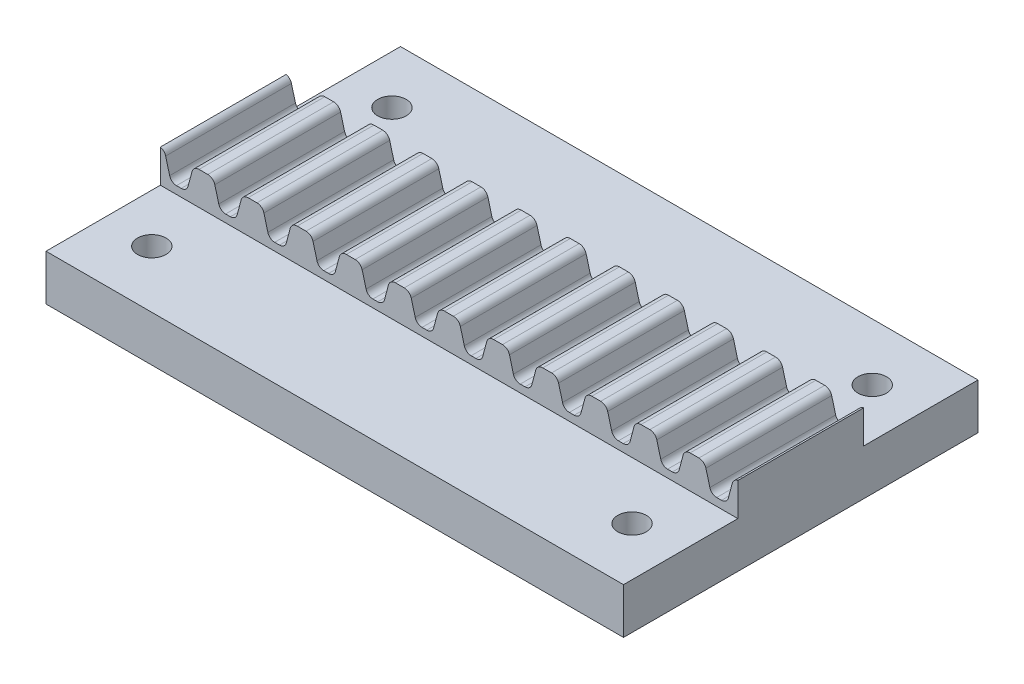
SolidWorks part; units mm, degrees
ref_plane "Front Plane" through (0, 0, 0) normal (0, 0, 1) x (1, 0, 0)
ref_plane "Top Plane" through (0, 0, 0) normal (0, 1, 0) x (1, 0, 0)
ref_plane "Right Plane" through (0, 0, 0) normal (1, 0, 0) x (0, 0, -1)
sketch "Sketch3" plane through (0, 0, 0) normal (1, 0, 0) x (0, 0, -1)
  line L1 (0, 0) -> (22, 0)
  line L2 (0, 0) -> (0, 5.7785)
  line L3 (0, 5.7785) -> (22, 5.7785)
  line L4 (22, 0) -> (22, 5.7785)
extrude "Boss-Extrude2" add sketch "Sketch3" against normal blind 101
sketch "Sketch5" plane through (0, 0, 0) normal (0, 0, -1) x (-1, 0, 0)
  line L0 (1.6741, 2.2584) -> (0.4213, 6.9342)
  line L1 (3.7054, 1.3462) -> (2.863, 1.3462)
  line L5 (4.8943, 2.2584) -> (6.1471, 6.9342)
  line L6 (0.4213, 6.9342) -> (6.1471, 6.9342)
  line L7 (10.2631, 2.2584) -> (9.0103, 6.9342)
  line L8 (9.0103, 6.9342) -> (14.7361, 6.9342)
  line L9 (13.4833, 2.2584) -> (14.7361, 6.9342)
  line L10 (12.2944, 1.3462) -> (11.452, 1.3462)
  line L11 (18.8521, 2.2584) -> (17.5993, 6.9342)
  line L12 (17.5993, 6.9342) -> (23.3251, 6.9342)
  line L13 (22.0723, 2.2584) -> (23.3251, 6.9342)
  line L14 (20.8834, 1.3462) -> (20.041, 1.3462)
  line L15 (27.4411, 2.2584) -> (26.1883, 6.9342)
  line L16 (26.1883, 6.9342) -> (31.9141, 6.9342)
  line L17 (30.6613, 2.2584) -> (31.9141, 6.9342)
  line L18 (29.4724, 1.3462) -> (28.63, 1.3462)
  line L19 (36.0301, 2.2584) -> (34.7773, 6.9342)
  line L20 (34.7773, 6.9342) -> (40.5031, 6.9342)
  line L21 (39.2503, 2.2584) -> (40.5031, 6.9342)
  line L22 (38.0614, 1.3462) -> (37.219, 1.3462)
  line L23 (44.6191, 2.2584) -> (43.3663, 6.9342)
  line L24 (43.3663, 6.9342) -> (49.0921, 6.9342)
  line L25 (47.8393, 2.2584) -> (49.0921, 6.9342)
  line L26 (46.6504, 1.3462) -> (45.808, 1.3462)
  line L27 (53.2081, 2.2584) -> (51.9553, 6.9342)
  line L28 (51.9553, 6.9342) -> (57.6811, 6.9342)
  line L29 (56.4283, 2.2584) -> (57.6811, 6.9342)
  line L30 (55.2394, 1.3462) -> (54.397, 1.3462)
  line L31 (61.7971, 2.2584) -> (60.5443, 6.9342)
  line L32 (60.5443, 6.9342) -> (66.2701, 6.9342)
  line L33 (65.0173, 2.2584) -> (66.2701, 6.9342)
  line L34 (63.8284, 1.3462) -> (62.986, 1.3462)
  line L35 (70.3861, 2.2584) -> (69.1333, 6.9342)
  line L36 (69.1333, 6.9342) -> (74.8591, 6.9342)
  line L37 (73.6063, 2.2584) -> (74.8591, 6.9342)
  line L38 (72.4174, 1.3462) -> (71.575, 1.3462)
  line L39 (78.9751, 2.2584) -> (77.7223, 6.9342)
  line L40 (77.7223, 6.9342) -> (83.4481, 6.9342)
  line L41 (82.1953, 2.2584) -> (83.4481, 6.9342)
  line L42 (81.0064, 1.3462) -> (80.164, 1.3462)
  line L43 (87.5641, 2.2584) -> (86.3113, 6.9342)
  line L44 (86.3113, 6.9342) -> (92.0371, 6.9342)
  line L45 (90.7843, 2.2584) -> (92.0371, 6.9342)
  line L46 (89.5954, 1.3462) -> (88.753, 1.3462)
  line L47 (96.1531, 2.2584) -> (94.9003, 6.9342)
  line L48 (94.9003, 6.9342) -> (100.6261, 6.9342)
  line L49 (99.3733, 2.2584) -> (100.6261, 6.9342)
  line L50 (98.1844, 1.3462) -> (97.342, 1.3462)
  arc A0 (3.7054, 1.3462) -> (4.8943, 2.2584) centre (3.7054, 2.577) ccw
  arc A1 (2.863, 1.3462) -> (1.6741, 2.2584) centre (2.863, 2.577) cw
  arc A2 (12.2944, 1.3462) -> (13.4833, 2.2584) centre (12.2944, 2.577) ccw
  arc A3 (11.452, 1.3462) -> (10.2631, 2.2584) centre (11.452, 2.577) cw
  arc A4 (20.8834, 1.3462) -> (22.0723, 2.2584) centre (20.8834, 2.577) ccw
  arc A5 (20.041, 1.3462) -> (18.8521, 2.2584) centre (20.041, 2.577) cw
  arc A6 (29.4724, 1.3462) -> (30.6613, 2.2584) centre (29.4724, 2.577) ccw
  arc A7 (28.63, 1.3462) -> (27.4411, 2.2584) centre (28.63, 2.577) cw
  arc A8 (38.0614, 1.3462) -> (39.2503, 2.2584) centre (38.0614, 2.577) ccw
  arc A9 (37.219, 1.3462) -> (36.0301, 2.2584) centre (37.219, 2.577) cw
  arc A10 (46.6504, 1.3462) -> (47.8393, 2.2584) centre (46.6504, 2.577) ccw
  arc A11 (45.808, 1.3462) -> (44.6191, 2.2584) centre (45.808, 2.577) cw
  arc A12 (55.2394, 1.3462) -> (56.4283, 2.2584) centre (55.2394, 2.577) ccw
  arc A13 (54.397, 1.3462) -> (53.2081, 2.2584) centre (54.397, 2.577) cw
  arc A14 (63.8284, 1.3462) -> (65.0173, 2.2584) centre (63.8284, 2.577) ccw
  arc A15 (62.986, 1.3462) -> (61.7971, 2.2584) centre (62.986, 2.577) cw
  arc A16 (72.4174, 1.3462) -> (73.6063, 2.2584) centre (72.4174, 2.577) ccw
  arc A17 (71.575, 1.3462) -> (70.3861, 2.2584) centre (71.575, 2.577) cw
  arc A18 (81.0064, 1.3462) -> (82.1953, 2.2584) centre (81.0064, 2.577) ccw
  arc A19 (80.164, 1.3462) -> (78.9751, 2.2584) centre (80.164, 2.577) cw
  arc A20 (89.5954, 1.3462) -> (90.7843, 2.2584) centre (89.5954, 2.577) ccw
  arc A21 (88.753, 1.3462) -> (87.5641, 2.2584) centre (88.753, 2.577) cw
  arc A22 (98.1844, 1.3462) -> (99.3733, 2.2584) centre (98.1844, 2.577) ccw
  arc A23 (97.342, 1.3462) -> (96.1531, 2.2584) centre (97.342, 2.577) cw
  dimension "D1" = 12
extrude "Cut-Extrude1" cut sketch "Sketch5" along normal through all
fillet "Fillet1" radius 1.2637 24 edges at (-100.3165, 5.7785, -11) (-95.2099, 5.7785, -11) (-91.7275, 5.7785, -11) (-86.6209, 5.7785, -11) (-83.1385, 5.7785, -11) (-78.0319, 5.7785, -11) (-74.5495, 5.7785, -11) (-69.4429, 5.7785, -11) (-65.9605, 5.7785, -11) (-60.8539, 5.7785, -11) (-57.3715, 5.7785, -11) (-52.2649, 5.7785, -11) (-48.7825, 5.7785, -11) (-43.6759, 5.7785, -11) (-40.1935, 5.7785, -11) (-35.0869, 5.7785, -11) (-31.6045, 5.7785, -11) (-26.4979, 5.7785, -11) (-23.0155, 5.7785, -11) (-17.9089, 5.7785, -11) (-14.4265, 5.7785, -11) (-9.3199, 5.7785, -11) (-5.8375, 5.7785, -11) (-0.7309, 5.7785, -11)
sketch "Sketch10" plane through (0, 0, 0) normal (0, 1, 0) x (1, 0, 0)
  line L1 (0, -20) -> (-101, -20)
  line L2 (0, -20) -> (0, 42)
  line L3 (0, 42) -> (-101, 42)
  line L4 (-101, -20) -> (-101, 42)
extrude "Boss-Extrude6" add sketch "Sketch10" against normal blind 8
sketch "Sketch11" plane through (0, 0, 0) normal (0, 1, 0) x (1, 0, 0)
  circle A0 centre (-8.5, -10) radius 2.5
  circle A7 centre (-92.5, -10) radius 2.5
  circle A8 centre (-80.5, -10) radius 2.5 [skipped]
  circle A9 centre (-68.5, -10) radius 2.5 [skipped]
  circle A10 centre (-56.5, -10) radius 2.5 [skipped]
  circle A11 centre (-44.5, -10) radius 2.5 [skipped]
  circle A12 centre (-32.5, -10) radius 2.5 [skipped]
  circle A13 centre (-20.5, -10) radius 2.5 [skipped]
  dimension "D1" = 8
sketch "Sketch12" plane through (0, 0, 0) normal (0, 1, 0) x (1, 0, 0)
  circle A0 centre (-8.5, 32) radius 2.5
  circle A7 centre (-92.5, 32) radius 2.5
  circle A8 centre (-80.5, 32) radius 2.5 [skipped]
  circle A9 centre (-68.5, 32) radius 2.5 [skipped]
  circle A10 centre (-56.5, 32) radius 2.5 [skipped]
  circle A11 centre (-44.5, 32) radius 2.5 [skipped]
  circle A12 centre (-32.5, 32) radius 2.5 [skipped]
  circle A13 centre (-20.5, 32) radius 2.5 [skipped]
  dimension "D1" = 8
extrude "Cut-Extrude2" cut sketch "Sketch11" against normal through all
extrude "Cut-Extrude3" cut sketch "Sketch12" against normal through all
